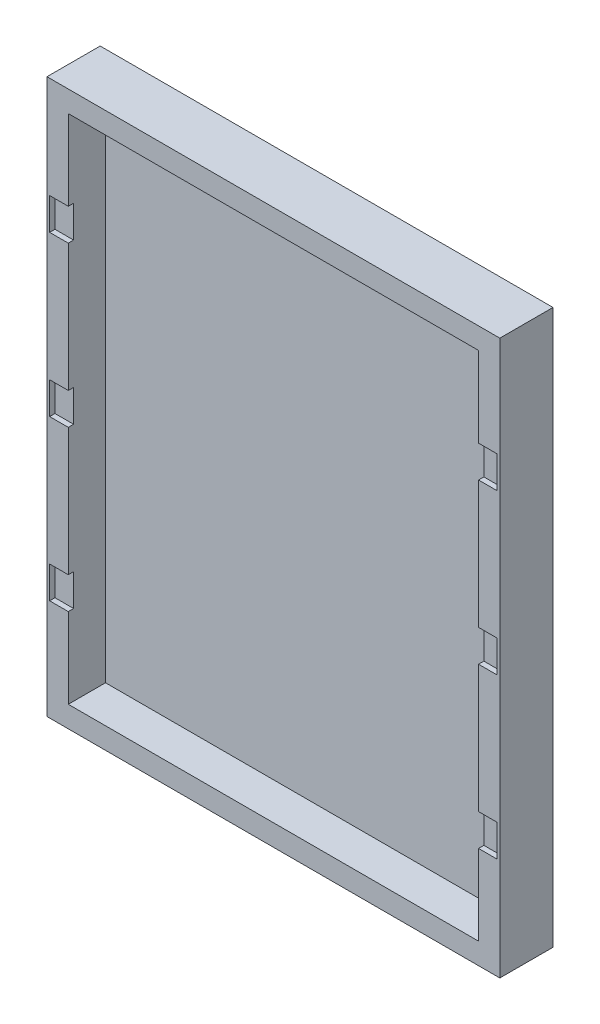
SolidWorks part; units mm, degrees
ref_plane "前视基准面" through (0, 0, 0) normal (0, 0, 1) x (1, 0, 0)
ref_plane "上视基准面" through (0, 0, 0) normal (0, 1, 0) x (1, 0, 0)
ref_plane "右视基准面" through (0, 0, 0) normal (1, 0, 0) x (0, 0, -1)
other "Configuration Table"
sketch "Model" plane through (0, 0, 0) normal (0, 0, 1) x (1, 0, 0)
  line L0 (-4.3804, 99.9831) -> (80.769, 99.9831)
  line L1 (80.769, -4.2164) -> (80.769, 99.9831)
  line L2 (-4.3804, -4.2164) -> (80.769, -4.2164)
  line L3 (-4.3804, -4.2164) -> (-4.3804, 99.9831)
  line L164 (-0.3804, 95.9831) -> (76.769, 95.9831)
  line L165 (-0.3804, -0.2164) -> (-0.3804, 95.9831)
  line L166 (-0.3804, -0.2164) -> (76.769, -0.2164)
  line L167 (76.769, -0.2164) -> (76.769, 95.9831)
  dimension "D1" = 77.1493
  dimension "D2" = 96.1995
  dimension "D3" = 4
extrude "凸台-拉伸2" add sketch "Model" along normal blind 7
sketch "草图1" plane through (0, 0, 0) normal (0, 0, -1) x (-1, 0, 0)
  line L1 (-80.769, 99.9831) -> (4.3804, 99.9831)
  line L2 (-80.769, 99.9831) -> (-80.769, -4.2164)
  line L3 (-80.769, -4.2164) -> (4.3804, -4.2164)
  line L4 (4.3804, 99.9831) -> (4.3804, -4.2164)
extrude "凸台-拉伸3" add sketch "草图1" along normal blind 3
sketch "草图2" plane through (0, 0, 7) normal (0, 0, 1) x (1, 0, 0)
  line L0 (-0.3804, 95.9831) -> (-0.3804, -0.2164) construction
  line L1 (-3.8804, 80.8834) -> (-0.3804, 80.8834)
  line L2 (-3.8804, 80.8834) -> (-3.8804, 74.8834)
  line L3 (-3.8804, 74.8834) -> (-0.3804, 74.8834)
  line L4 (-0.3804, 80.8834) -> (-0.3804, 74.8834)
  line L5 (-3.3804, 80.3834) -> (-0.3804, 80.3834) construction
  line L6 (-3.3804, 75.3834) -> (-3.3804, 80.3834) construction
  line L7 (-0.3804, 75.3834) -> (-3.3804, 75.3834) construction
  line L9 (76.769, 80.8834) -> (76.769, 74.8834)
  line L10 (80.269, 74.8834) -> (76.769, 74.8834)
  line L11 (80.269, 80.8834) -> (80.269, 74.8834)
  line L12 (80.269, 80.8834) -> (76.769, 80.8834)
  line L13 (-3.8804, 50.8834) -> (-0.3803, 50.8834)
  line L14 (-3.8804, 50.8834) -> (-3.8804, 44.8834)
  line L15 (-3.8804, 44.8834) -> (-0.3803, 44.8834)
  line L16 (-0.3803, 50.8834) -> (-0.3803, 44.8834)
  line L17 (76.769, 50.8834) -> (76.769, 44.8834)
  line L18 (80.269, 44.8834) -> (76.769, 44.8834)
  line L19 (80.269, 50.8834) -> (80.269, 44.8834)
  line L20 (80.269, 50.8834) -> (76.769, 50.8834)
  line L21 (-3.8804, 20.8834) -> (-0.3803, 20.8834)
  line L22 (-3.8804, 20.8834) -> (-3.8804, 14.8834)
  line L23 (-3.8804, 14.8834) -> (-0.3803, 14.8834)
  line L24 (-0.3803, 20.8834) -> (-0.3803, 14.8834)
  line L25 (76.769, 20.8834) -> (76.769, 14.8834)
  line L26 (80.269, 14.8834) -> (76.769, 14.8834)
  line L27 (80.269, 20.8834) -> (80.269, 14.8834)
  line L28 (80.269, 20.8834) -> (76.769, 20.8834)
  dimension "D1" = 0.5
  dimension "D2" = 0.5
  dimension "D3" = 0.5
extrude "切除-拉伸1" cut sketch "草图2" against normal blind 1
